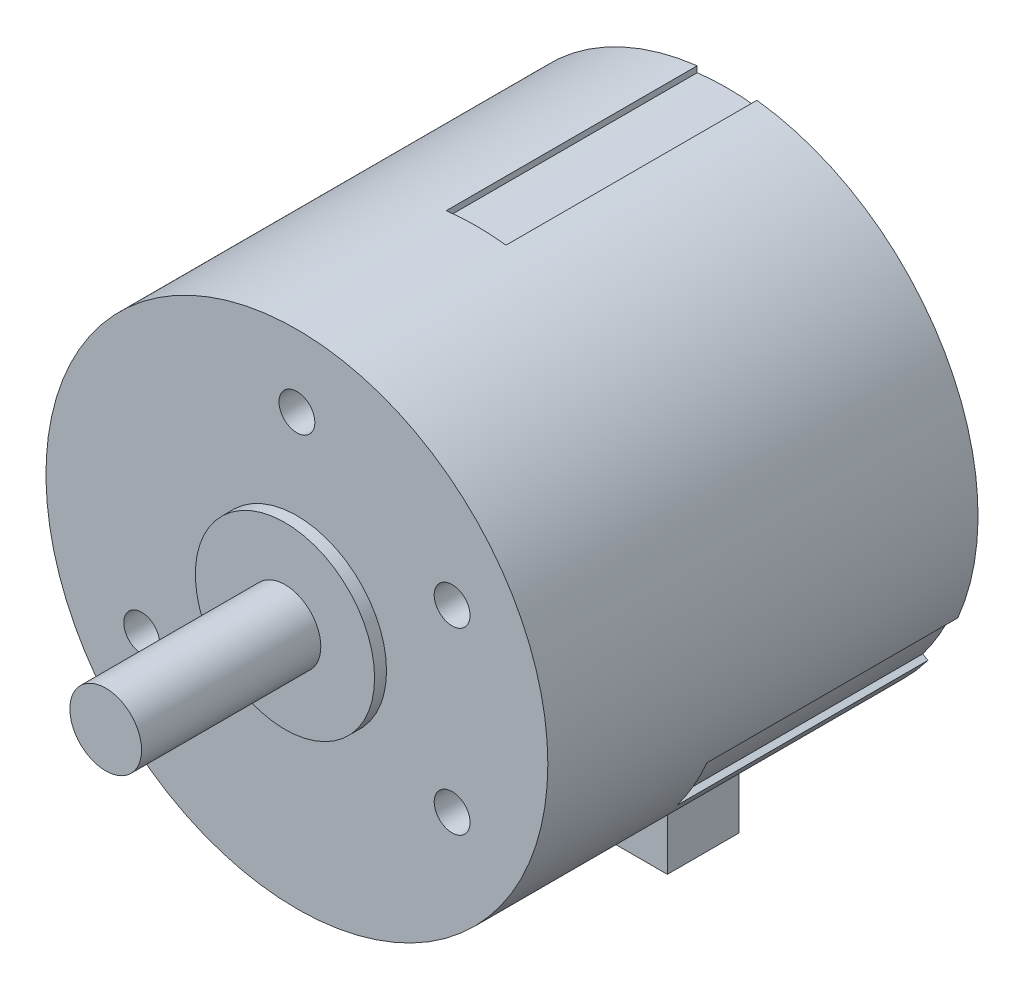
SolidWorks part; units mm, degrees
ref_plane "前视基准面" through (0, 0, 0) normal (0, 0, 1) x (1, 0, 0)
ref_plane "上视基准面" through (0, 0, 0) normal (0, 1, 0) x (1, 0, 0)
ref_plane "右视基准面" through (0, 0, 0) normal (1, 0, 0) x (0, 0, -1)
other "Configuration Table"
sketch "草图1" plane through (0, 0, 0) normal (0, 0, 1) x (1, 0, 0)
  circle A0 centre (0, 0) radius 21
extrude "凸台-拉伸1" add sketch "草图1" along normal blind 15
sketch "草图2" plane through (0, 0, 0) normal (0, 0, -1) x (-1, 0, 0)
  line L0 (2.5, 20.8507) -> (2.5, 20.347)
  line L1 (0, 8.25) -> (0, -8.25) construction
  line L2 (-2.5, 20.8507) -> (-2.5, 20.347)
  line L3 (19.3072, -8.2603) -> (18.871, -8.0084)
  line L4 (16.8072, -12.5904) -> (16.371, -12.3386)
  line L5 (-16.8072, -12.5904) -> (-16.371, -12.3386)
  line L6 (-19.3072, -8.2603) -> (-18.871, -8.0084)
  line L7 (15, -13.9732) -> (15, -14.6969)
  line L8 (-15, -13.9732) -> (-15, -14.6969)
  arc A0 (-2.5, 20.8507) -> (-19.3072, -8.2603) centre (0, 0) ccw
  circle A1 centre (0, 0) radius 21 construction
  arc A2 (-18.871, -8.0084) -> (-16.371, -12.3386) centre (0, 0) ccw
  arc A3 (19.3072, -8.2603) -> (2.5, 20.8507) centre (0, 0) ccw
  arc A4 (-16.8072, -12.5904) -> (-15, -14.6969) centre (0, 0) ccw
  arc A5 (15, -14.6969) -> (16.8072, -12.5904) centre (0, 0) ccw
  arc A6 (-15, -13.9732) -> (15, -13.9732) centre (0, 0) ccw
  arc A7 (16.371, -12.3386) -> (18.871, -8.0084) centre (0, 0) ccw
  arc A8 (2.5, 20.347) -> (-2.5, 20.347) centre (0, 0) ccw
  point P22 (0, 0)
  dimension "D1" = 5
  dimension "D2" = 3
  dimension "D3" = 30
extrude "凸台-拉伸2" add sketch "草图2" along normal blind 6
sketch "草图4" plane through (0, 0, -6) normal (0, 0, -1) x (-1, 0, 0)
  line L0 (10, -17.8955) -> (10, -24)
  line L1 (0, 11.55) -> (0, -11.55) construction
  line L2 (-10, -17.8955) -> (-10, -24)
  line L3 (-10, -24) -> (10, -24)
  line L8 (2.5, 20.8507) -> (2.5, 20.347)
  line L9 (-2.5, 20.347) -> (-2.5, 20.8507)
  line L10 (-19.3072, -8.2603) -> (-18.871, -8.0084)
  line L11 (-16.371, -12.3386) -> (-16.8072, -12.5904)
  line L12 (-15, -14.6969) -> (-15, -13.9732)
  line L13 (15, -13.9732) -> (15, -14.6969)
  line L14 (16.8072, -12.5904) -> (16.371, -12.3386)
  line L15 (18.871, -8.0084) -> (19.3072, -8.2603)
  line L16 (2.5, 20.8507) -> (2.5, 20.347)
  line L17 (-2.5, 20.347) -> (-2.5, 20.8507)
  line L18 (-19.3072, -8.2603) -> (-18.871, -8.0084)
  line L19 (-16.371, -12.3386) -> (-16.8072, -12.5904)
  line L20 (-15, -14.6969) -> (-15, -13.9732)
  line L21 (15, -13.9732) -> (15, -14.6969)
  line L22 (16.8072, -12.5904) -> (16.371, -12.3386)
  line L23 (18.871, -8.0084) -> (19.3072, -8.2603)
  arc A0 (10, -17.8955) -> (15, -13.9732) centre (0, 0) ccw
  arc A8 (19.3072, -8.2603) -> (2.5, 20.8507) centre (0, 0) ccw
  arc A9 (2.5, 20.347) -> (-2.5, 20.347) centre (0, 0) ccw
  arc A10 (-2.5, 20.8507) -> (-19.3072, -8.2603) centre (0, 0) ccw
  arc A11 (-18.871, -8.0084) -> (-16.371, -12.3386) centre (0, 0) ccw
  arc A12 (-16.8072, -12.5904) -> (-15, -14.6969) centre (0, 0) ccw
  arc A13 (-15, -13.9732) -> (15, -13.9732) centre (0, 0) ccw
  arc A14 (15, -14.6969) -> (16.8072, -12.5904) centre (0, 0) ccw
  arc A15 (16.371, -12.3386) -> (18.871, -8.0084) centre (0, 0) ccw
  arc A16 (19.3072, -8.2603) -> (2.5, 20.8507) centre (0, 0) ccw
  arc A17 (2.5, 20.347) -> (-2.5, 20.347) centre (0, 0) ccw
  arc A18 (-2.5, 20.8507) -> (-19.3072, -8.2603) centre (0, 0) ccw
  arc A19 (-18.871, -8.0084) -> (-16.371, -12.3386) centre (0, 0) ccw
  arc A20 (-16.8072, -12.5904) -> (-15, -14.6969) centre (0, 0) ccw
  arc A21 (-15, -13.9732) -> (-10, -17.8955) centre (0, 0) ccw
  arc A22 (15, -14.6969) -> (16.8072, -12.5904) centre (0, 0) ccw
  arc A23 (16.371, -12.3386) -> (18.871, -8.0084) centre (0, 0) ccw
  dimension "D2" = 20
  dimension "D3" = 24
  dimension "D1" = 0
extrude "凸台-拉伸3" add sketch "草图4" along normal blind 6
sketch "草图5" plane through (0, 0, -12) normal (0, 0, -1) x (-1, 0, 0)
  line L8 (18.871, -8.0084) -> (19.3072, -8.2603)
  line L9 (2.5, 20.8507) -> (2.5, 20.347)
  line L10 (-2.5, 20.347) -> (-2.5, 20.8507)
  line L11 (-19.3072, -8.2603) -> (-18.871, -8.0084)
  line L12 (-16.371, -12.3386) -> (-16.8072, -12.5904)
  line L13 (-15, -14.6969) -> (-15, -13.9732)
  line L14 (15, -13.9732) -> (15, -14.6969)
  line L15 (16.8072, -12.5904) -> (16.371, -12.3386)
  line L16 (18.871, -8.0084) -> (19.3072, -8.2603)
  line L17 (2.5, 20.8507) -> (2.5, 20.347)
  line L18 (-2.5, 20.347) -> (-2.5, 20.8507)
  line L19 (-19.3072, -8.2603) -> (-18.871, -8.0084)
  line L20 (-16.371, -12.3386) -> (-16.8072, -12.5904)
  line L23 (16.8072, -12.5904) -> (16.371, -12.3386)
  arc A0 (-15, -14.6969) -> (15, -14.6969) centre (0, 0) ccw
  arc A1 (-15, -14.6969) -> (15, -14.6969) centre (0, 0) ccw construction
  arc A8 (19.3072, -8.2603) -> (2.5, 20.8507) centre (0, 0) ccw
  arc A9 (2.5, 20.347) -> (-2.5, 20.347) centre (0, 0) ccw
  arc A10 (-2.5, 20.8507) -> (-19.3072, -8.2603) centre (0, 0) ccw
  arc A11 (-18.871, -8.0084) -> (-16.371, -12.3386) centre (0, 0) ccw
  arc A12 (-16.8072, -12.5904) -> (-15, -14.6969) centre (0, 0) ccw
  arc A13 (-15, -13.9732) -> (15, -13.9732) centre (0, 0) ccw
  arc A14 (15, -14.6969) -> (16.8072, -12.5904) centre (0, 0) ccw
  arc A15 (16.371, -12.3386) -> (18.871, -8.0084) centre (0, 0) ccw
  arc A16 (19.3072, -8.2603) -> (2.5, 20.8507) centre (0, 0) ccw
  arc A17 (2.5, 20.347) -> (-2.5, 20.347) centre (0, 0) ccw
  arc A18 (-2.5, 20.8507) -> (-19.3072, -8.2603) centre (0, 0) ccw
  arc A19 (-18.871, -8.0084) -> (-16.371, -12.3386) centre (0, 0) ccw
  arc A20 (-16.8072, -12.5904) -> (-15, -14.6969) centre (0, 0) ccw
  arc A22 (15, -14.6969) -> (16.8072, -12.5904) centre (0, 0) ccw
  arc A23 (16.371, -12.3386) -> (18.871, -8.0084) centre (0, 0) ccw
  dimension "D1" = 0
extrude "凸台-拉伸4" add sketch "草图5" along normal blind 9
sketch "草图6" plane through (0, 0, 15) normal (0, 0, 1) x (1, 0, 0)
  circle A0 centre (0, 0) radius 7.5
  dimension "D1" = 15
extrude "凸台-拉伸5" add sketch "草图6" along normal blind 1
sketch "草图7" plane through (0, 0, 16) normal (0, 0, 1) x (1, 0, 0)
  circle A0 centre (0, 0) radius 3
extrude "凸台-拉伸6" add sketch "草图7" along normal blind 15
sketch "草图8" plane through (0, 0, 15) normal (0, 0, 1) x (1, 0, 0)
  circle A0 centre (0, 0) radius 15 construction
  circle A1 centre (0, 15) radius 1.5
  circle A2 centre (12.9904, 7.5) radius 1.5
  circle A3 centre (12.9904, -7.5) radius 1.5
  circle A4 centre (-12.9904, -7.5) radius 1.5
  point P14 (0, 0)
  dimension "D1" = 15
  dimension "D4" = 30
  dimension "D2" = 15
  dimension "D3" = 2
extrude "切除-拉伸1" cut sketch "草图8" against normal blind 3
